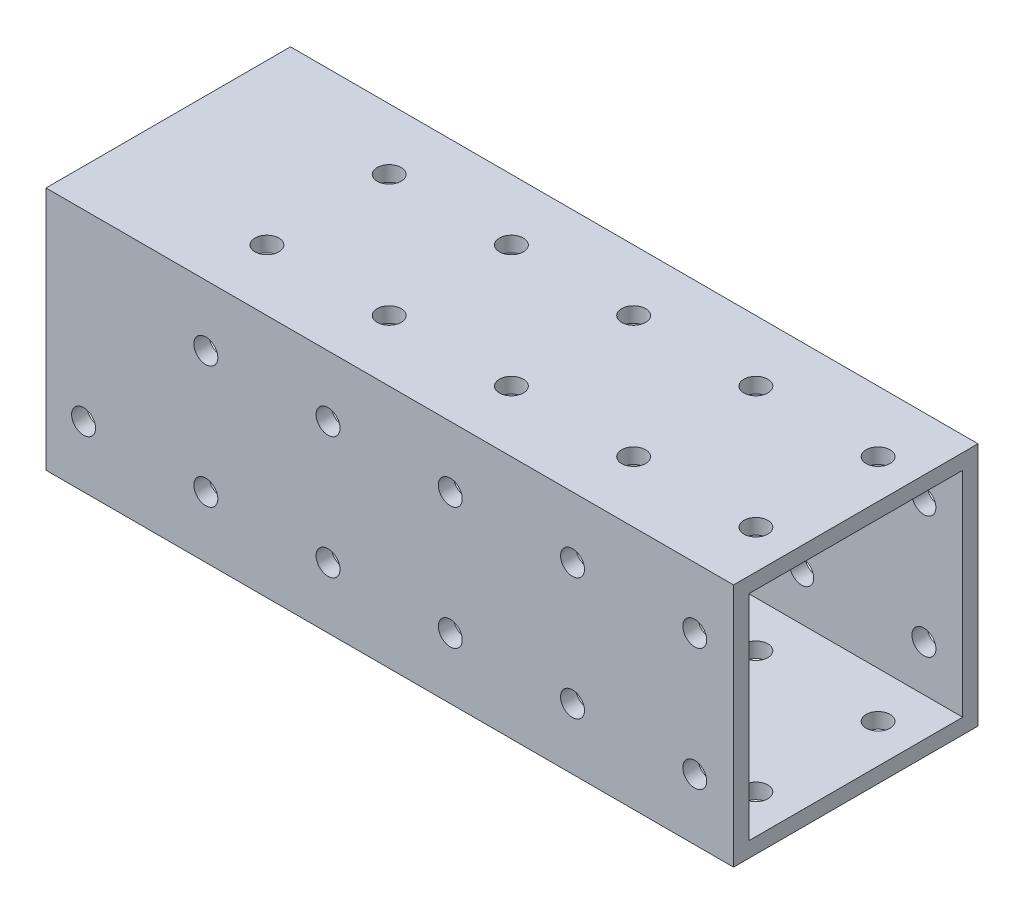
SolidWorks part; units mm, degrees
material "6061-T6 (SS)"
ref_plane "Front Plane" through (0, 0, 0) normal (0, 0, 1) x (1, 0, 0)
ref_plane "Top Plane" through (0, 0, 0) normal (0, 1, 0) x (1, 0, 0)
ref_plane "Right Plane" through (0, 0, 0) normal (1, 0, 0) x (0, 0, -1)
sketch "Sketch1" plane through (0, 0, 0) normal (1, 0, 0) x (0, 0, -1)
  line L1 (0, 0) -> (50.8, 0)
  line L2 (0, 0) -> (0, 50.8)
  line L3 (0, 50.8) -> (50.8, 50.8)
  line L4 (50.8, 0) -> (50.8, 50.8)
  dimension "D1" = 50.8
extrude "Boss-Extrude1" add sketch "Sketch1" along normal blind 142.875
shell "Shell1" thickness 3.175 removed face at (0, 25.4, -25.4) removed face at (142.875, 25.4, -25.4)
sketch "Sketch2" plane through (0, 0, -50.8) normal (0, 0, -1) x (-1, 0, 0)
  circle A0 centre (-134.8133, 38.1) radius 2.4892 construction
  circle A1 centre (-109.4133, 38.1) radius 2.4892 construction
  circle A2 centre (-84.0133, 38.1) radius 2.4892 construction
  circle A3 centre (-58.6133, 38.1) radius 2.4892 construction
  circle A4 centre (-33.2133, 38.1) radius 2.4892 construction
  circle A5 centre (-33.2133, 12.7) radius 2.4892 construction
  circle A6 centre (-58.6133, 12.7) radius 2.4892 construction
  circle A7 centre (-84.0133, 12.7) radius 2.4892 construction
  circle A8 centre (-109.4133, 12.7) radius 2.4892 construction
  circle A9 centre (-134.8133, 12.7) radius 2.4892 construction
  circle A10 centre (-134.8133, 38.1) radius 2.4892
  circle A11 centre (-109.4133, 38.1) radius 2.4892
  circle A12 centre (-84.0133, 38.1) radius 2.4892
  circle A13 centre (-58.6133, 38.1) radius 2.4892
  circle A14 centre (-33.2133, 38.1) radius 2.4892
  circle A15 centre (-33.2133, 12.7) radius 2.4892
  circle A16 centre (-58.6133, 12.7) radius 2.4892
  circle A17 centre (-84.0133, 12.7) radius 2.4892
  circle A18 centre (-109.4133, 12.7) radius 2.4892
  circle A19 centre (-134.8133, 12.7) radius 2.4892
  circle A20 centre (-7.8133, 12.7) radius 2.4892 construction
  circle A21 centre (-7.8133, 12.7) radius 2.4892
extrude "Cut-Extrude1" cut sketch "Sketch2" against normal through all
sketch "Sketch3" plane through (0, 0, 0) normal (0, -1, 0) x (1, 0, 0)
  line L1 (134.8133, -38.1) -> (134.8133, -12.7) construction
  line L2 (134.8133, -12.7) -> (134.8133, 12.7) construction
  line L3 (293.5633, 0) -> (-303.3367, 0) construction
  line L4 (142.875, -50.8) -> (0, -50.8) construction
  circle A0 centre (134.8133, -12.7) radius 2.4892
  circle A1 centre (134.8133, -38.1) radius 2.4892
  dimension "D1" = 4.9784
  dimension "D2" = 12.7
  dimension "D3" = 12.7
extrude "Cut-Extrude2" cut sketch "Sketch3" against normal through all
pattern_linear "LPattern1" count 5 spacing 25.4 along (-1, 0, 0) of "Cut-Extrude2"
